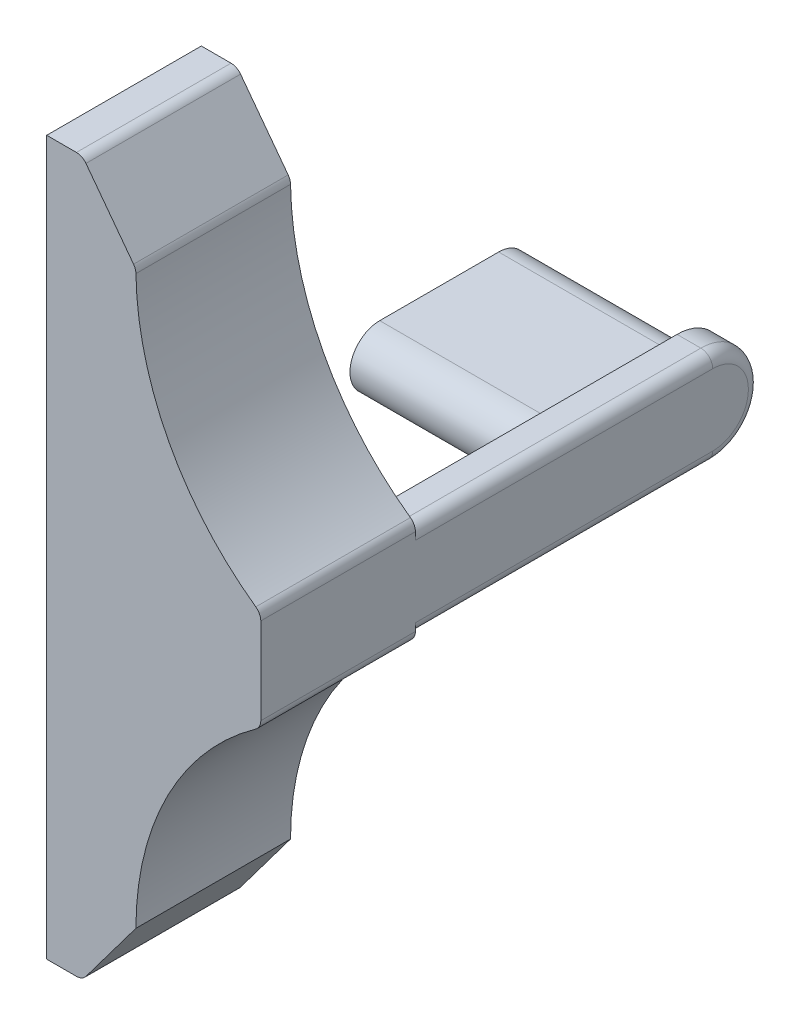
SolidWorks part; units mm, degrees
ref_plane "前视基准面" through (0, 0, 0) normal (0, 0, 1) x (1, 0, 0)
ref_plane "上视基准面" through (0, 0, 0) normal (0, 1, 0) x (1, 0, 0)
ref_plane "右视基准面" through (0, 0, 0) normal (1, 0, 0) x (0, 0, -1)
other "Configuration Table"
sketch "草图1" plane through (0, 0, 0) normal (0, 0, 1) x (1, 0, 0)
  line L0 (-15, 530.2441) -> (-15, -349.7559) construction
  line L1 (-15, 530.2441) -> (-15, -349.7559) construction
  line L2 (-15, 90.2441) -> (72.1541, 90.2441) construction
  line L3 (-7.5, 195.623) -> (-7.5, 36.6092) construction
  line L4 (-7.5, 114.2441) -> (-12, 120.2441)
  line L5 (-12, 120.2441) -> (-15, 120.2441)
  line L6 (-15, 120.2441) -> (-15, 60.2441)
  line L7 (0, 530.2441) -> (0, -349.7559) construction
  line L8 (0, 530.2441) -> (0, -349.7559) construction
  line L9 (3, 94.4009) -> (3, 86.0872)
  line L10 (-7.5, 66.2441) -> (-12, 60.2441)
  line L11 (-12, 60.2441) -> (-15, 60.2441)
  arc A0 (-7.5, 114.2441) -> (3, 94.4009) centre (16.5, 114.2441) ccw
  arc A1 (-7.5, 66.2441) -> (3, 86.0872) centre (16.5, 66.2441) cw
  point P2 (-15, 90.2441)
  point P16 (0, 90.2441)
  dimension "D2" = 24
  dimension "D1" = 7.5
  dimension "D3" = 30
  dimension "D4" = 3
  dimension "D5" = 3
extrude "凸台-拉伸1" add sketch "草图1" along normal blind 13
sketch "草图3" plane through (3, 0, 0) normal (1, 0, 0) x (0, 0, -1)
  line L0 (15, 92.7441) -> (25, 92.7441) construction
  line L1 (15, 87.7441) -> (25, 87.7441) construction
  line L2 (15, 87.7441) -> (25, 87.7441) construction
  line L3 (15, 92.7441) -> (25, 92.7441) construction
  line L4 (-13, 86.0872) -> (-13, 94.4009) construction
  line L5 (1, 86.2441) -> (-9, 86.2441)
  line L6 (15, 94.2441) -> (25, 94.2441)
  line L7 (15, 86.2441) -> (25, 86.2441)
  line L8 (8, 101.2641) -> (8, 78.4371) construction
  line L9 (1, 94.2441) -> (-9, 94.2441)
  line L10 (15, 94.2441) -> (1, 94.2441)
  line L11 (15, 86.2441) -> (1, 86.2441)
  arc A0 (25, 87.7441) -> (25, 92.7441) centre (25, 90.2441) ccw construction
  arc A1 (25, 87.7441) -> (25, 92.7441) centre (25, 90.2441) ccw construction
  arc A2 (25, 86.2441) -> (25, 94.2441) centre (25, 90.2441) ccw
  arc A3 (-9, 86.2441) -> (-9, 94.2441) centre (-9, 90.2441) cw
  dimension "D2" = 1.5
  dimension "D1" = 21
extrude "凸台-拉伸2" add sketch "草图3" against normal up to surface (3 mm away)
sketch "草图4" plane through (0, 0, 0) normal (-1, 0, 0) x (0, 0, 1)
  line L2 (-15, 92.7441) -> (-25, 92.7441)
  line L3 (-25, 87.7441) -> (-15, 87.7441)
  line L4 (-15, 92.7441) -> (-25, 92.7441)
  line L5 (-25, 87.7441) -> (-15, 87.7441)
  arc A2 (-25, 92.7441) -> (-25, 87.7441) centre (-25, 90.2441) ccw
  arc A3 (-15, 87.7441) -> (-15, 92.7441) centre (-15, 90.2441) ccw
  arc A4 (-25, 92.7441) -> (-25, 87.7441) centre (-25, 90.2441) ccw
  arc A5 (-15, 87.7441) -> (-15, 92.7441) centre (-15, 90.2441) ccw
  dimension "D1" = 0
extrude "凸台-拉伸3" add sketch "草图4" along normal up to surface (15 mm away)
fillet "圆角1" radius 1 1 edges at (3, 94.4009, 6.5)
fillet "圆角2" radius 1 1 edges at (3, 86.0872, 6.5)
fillet "圆角3" radius 1 3 edges at (2.9308, 86.2441, -12.5) (3, 90.2441, -29) (2.9308, 94.2441, -12.5)
fillet "圆角4" radius 1 1 edges at (-12, 60.2441, 6.5)
fillet "圆角5" radius 1 1 edges at (-12, 120.2441, 6.5)
fillet "圆角8" radius 1 1 edges at (-7.5, 114.2441, 6.5)
